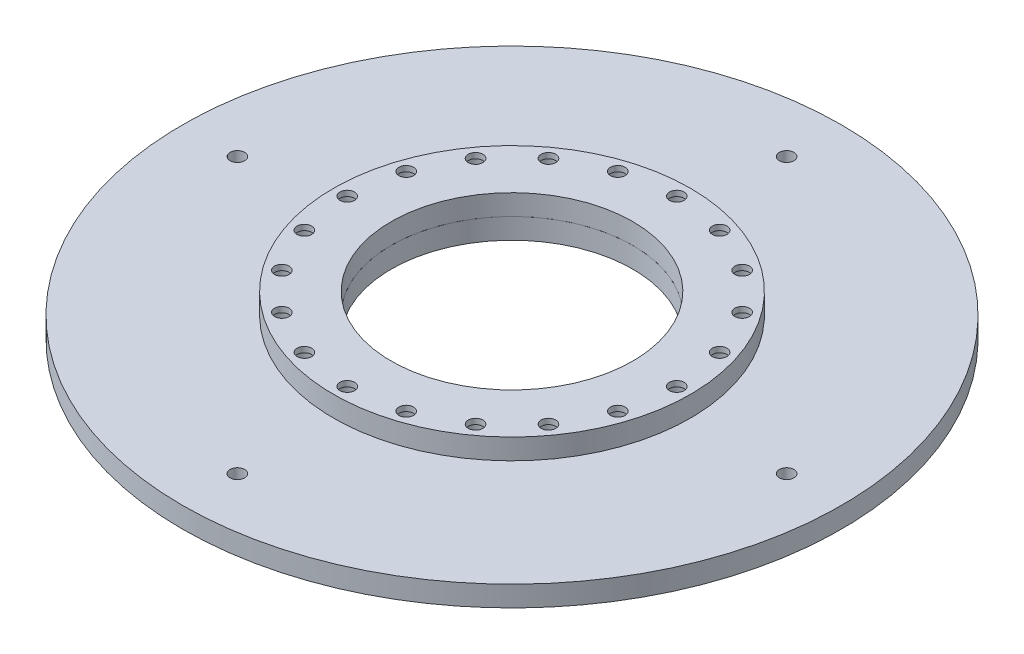
SolidWorks part; units mm, degrees
ref_plane "Front Plane" through (0, 0, 0) normal (0, 0, 1) x (1, 0, 0)
ref_plane "Top Plane" through (0, 0, 0) normal (0, 1, 0) x (1, 0, 0)
ref_plane "Right Plane" through (0, 0, 0) normal (1, 0, 0) x (0, 0, -1)
sketch "Sketch9" plane through (0, 0, 0) normal (0, 1, 0) x (1, 0, 0)
  circle A2 centre (0, 0) radius 82.55
  circle A4 centre (0, 0) radius 55.88
  circle A5 centre (0, 0) radius 76.2 construction
  point P6 (0, 76.2)
  point P34 (0, 0)
  dimension "Diameter_BackPlate" = 165.1
  dimension "Diameter_FuelOuterPlenum" = 111.76
  dimension "Diameter_BackPlate_BoltCircle" = 152.4
extrude "REF_BackPlate" add sketch "Sketch9" along normal blind 9.525 contours A2 A4 region at (-80.2151, 0, 0)
sketch "Sketch1" plane through (0, 0, 0) normal (0, 1, 0) x (1, 0, 0)
  line L1 (0, 82.55) -> (0, 81.788) construction
  line L2 (0, 81.788) -> (0, 76.2) construction
  line L3 (3.7419, 72.0498) -> (10.2656, 64.8143) construction
  line L5 (3.7419, 72.0498) -> (0, 76.2) construction
  line L6 (8.7416, 55.192) -> (10.2656, 64.8143) construction
  line L7 (0, 82.55) -> (0, 127) construction
  line L8 (39.2452, 120.7842) -> (25.5094, 78.5097) construction
  line L9 (8.7416, 55.192) -> (0, 0) construction
  line L12 (10.2656, 64.8143) -> (18.7059, 69.6798) construction
  line L13 (18.7059, 69.6798) -> (23.5471, 72.4705) construction
  circle A3 centre (0, 0) radius 152.4
  circle A8 centre (0, 0) radius 127 construction
  circle A14 centre (0, 76.2) radius 5.588 construction
  circle A15 centre (0, 0) radius 55.88 construction
  circle A17 centre (0, 0) radius 82.55 construction
  circle A18 centre (23.5471, 72.4705) radius 5.588 construction
  circle A19 centre (0, 0) radius 76.2 construction
  circle A20 centre (0, 0) radius 55.88
  point P2 (0, 127)
  point P5 (10.2656, 64.8143)
  dimension "Diameter_Takeout_BoltCircle" = 254
  dimension "Diameter_ThrustPlate" = 304.8
  dimension "D1" = 11.176
  dimension "D3" = 18
sketch "Sketch20" plane through (0, 0, 0) normal (0, -1, 0) x (-1, 0, 0)
  point P0 (0, 76.2)
hole_wizard "REF_CBORE_BackPlate" positions "Sketch20" profile "Sketch21" counterbore size "1/4" standard "ANSI Inch" end condition through all
sketch "Sketch21" plane through (0, 0, -76.2) normal (1, 0, 0) x (0, 0, -1)
  line L0 (0, 0) -> (0, 9.525)
  line L1 (0, 9.525) -> (3.3782, 9.525)
  line L3 (3.3782, 9.525) -> (3.3782, 6.985)
  line L4 (3.3782, 6.985) -> (5.588, 6.985)
  line L5 (5.588, 6.985) -> (5.588, 0)
  line L7 (5.588, 0) -> (0, 0)
  line L11 (0, -6.35) -> (0, 107.95) construction
  dimension "Thru Hole Dia." = 6.7564
  dimension "Thru Hole Depth" = 9.525
  dimension "C'Bore Dia." = 11.176
  dimension "C'Bore Depth" = 6.985
pattern_circular "REF_CBORE_BackPlate_Pattern" count 20 over 360 about axis through (0, 9.525, 0) along (0, -1, 0) of "REF_CBORE_BackPlate"
extrude "ThrustPlate_TC3" add sketch "Sketch1" against normal blind 9.525 separate body contours A3 region at (-148.0895, 0, 0)
sketch "Sketch11" plane through (0, 0, 0) normal (0, 1, 0) x (1, 0, 0)
  point P0 (0, 127)
hole_wizard "UNDEF_Clearance_ThrustPlate" positions "Sketch11" profile "Sketch12" hole size "1/4" standard "ANSI Inch" end condition through all
sketch "Sketch12" plane through (0, 0, -127) normal (1, 0, 0) x (0, 0, 1)
  line L0 (0, 0) -> (0, 9.525)
  line L1 (0, 9.525) -> (3.3782, 9.525)
  line L2 (3.3782, 9.525) -> (3.3782, 0)
  line L5 (3.3782, 0) -> (0, 0)
  line L11 (0, -6.35) -> (0, 107.95) construction
  dimension "Thru Hole Dia." = 6.7564
  dimension "Thru Hole Depth" = 9.525
pattern_circular "Clearance_ThrustPlate_Pattern" count 4 over 360 about axis through (0, -9.525, 0) along (0, 1, 0) of "UNDEF_Clearance_ThrustPlate" reverse direction yes
sketch "Sketch13" plane through (0, 0, 0) normal (0, 1, 0) x (1, 0, 0)
  point P0 (10.2656, 64.8143)
hole_wizard "UNDEF_Clearance_BackPlate" positions "Sketch13" profile "Sketch14" hole size "#12" standard "ANSI Inch" end condition through all
sketch "Sketch14" plane through (10.2656, 0, -64.8143) normal (1, 0, 0) x (0, 0, 1)
  line L0 (0, 0) -> (0, 9.525)
  line L1 (0, 9.525) -> (3.175, 9.525)
  line L2 (3.175, 9.525) -> (3.175, 0)
  line L5 (3.175, 0) -> (0, 0)
  line L11 (0, -6.35) -> (0, 107.95) construction
  dimension "Thru Hole Depth" = 9.525
  dimension "Thru Hole Dia." = 6.35
pattern_circular "UNDEF_Clearance_BackPlate_Pattern" count 10 over 360 about axis through (0, -9.525, 0) along (0, 1, 0) of "UNDEF_Clearance_BackPlate" reverse direction yes
equation "\"Diameter_BackPlate\"= 6.5"
equation "\"VAR_Diameter_BackPlate_BoltCircle\"= 6"
equation "\"VAR_Diameter_FuelOuterPlenum\"= 4.4"
equation "\"Diameter_BackPlate@Sketch9\"=\"Diameter_BackPlate\""
equation "\"Diameter_BackPlate_BoltCircle@Sketch9\"=\"VAR_Diameter_BackPlate_BoltCircle\""
equation "\"Diameter_FuelOuterPlenum@Sketch9\"=\"VAR_Diameter_FuelOuterPlenum\""
equation "\"Thickness_ThrustPlate\"= 0.375'undetermined"
equation "\"Diameter_ThrustPlate\"= 12'defined"
equation "\"Diameter_Takeout_BoltCicle\"= 10'defined"
equation "\"Diameter_Takeout_BoltCircle@Sketch1\"=\"Diameter_Takeout_BoltCicle\""
equation "\"Diameter_ThrustPlate@Sketch1\"=\"Diameter_ThrustPlate\""
equation "\"D1@ThrustPlate_TC3\"=\"Thickness_ThrustPlate\""
equation "\"VAR_Diameter_CBORE\"= 0.44'undetermined"
equation "\"VAR_Diameter_Clearance_ThrustPlate\"= 0.25'undetermined"
equation "\"D3@Sketch1\"=360/\"D1@REF_CBORE_BackPlate_Pattern\""
equation "\"D1@Sketch1\"=\"C'Bore Dia.@Sketch21\"''''''''''''''''''"
equation "\"C'Bore Dia.@Sketch21\"=\"VAR_Diameter_CBORE\""
equation "\"Thru Hole Dia.@Sketch14\"=\"VAR_Diameter_Clearance_ThrustPlate\""
equation "\"NumberBolts_BackPlate\"= 20"
equation "\"NumberBolts_Takeout\"= 4'defined"
equation "\"D1@Clearance_ThrustPlate_Pattern\"=\"NumberBolts_Takeout\""
equation "\"D1@REF_CBORE_BackPlate_Pattern\"=\"NumberBolts_BackPlate\""
equation "\"D1@UNDEF_Clearance_BackPlate_Pattern\"=\"NumberBolts_BackPlate\"/2"
equation "\"D1@CirPattern4\"=\"D1@UNDEF_Clearance_BackPlate_Pattern\""
